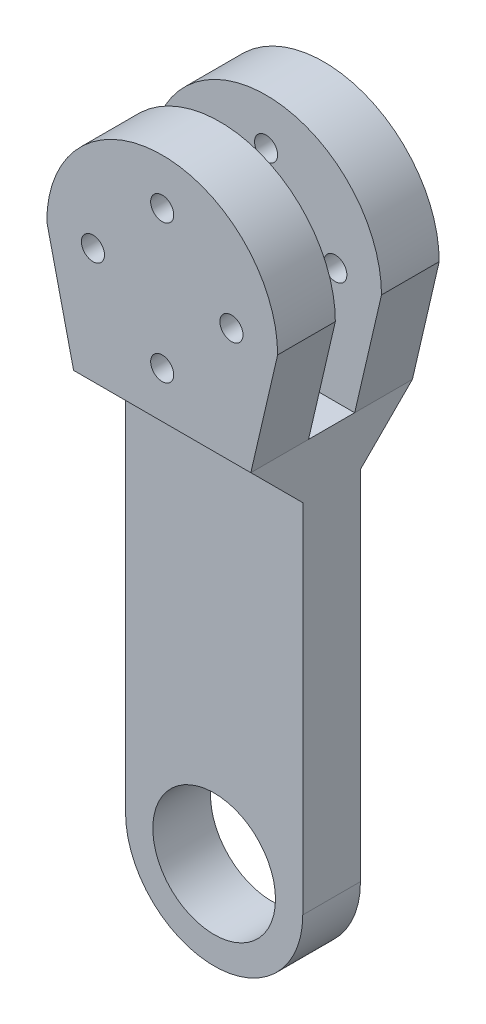
SolidWorks part; units mm, degrees
ref_plane "Front Plane" through (0, 0, 0) normal (0, 0, 1) x (1, 0, 0)
ref_plane "Top Plane" through (0, 0, 0) normal (0, 1, 0) x (1, 0, 0)
ref_plane "Right Plane" through (0, 0, 0) normal (1, 0, 0) x (0, 0, -1)
sketch "Sketch1" plane through (0, 0, 0) normal (0, 0, 1) x (1, 0, 0)
  line L0 (-9.75, 0) -> (-9.75, 45)
  line L1 (-9.75, 45) -> (9.75, 45)
  line L2 (9.75, 45) -> (9.75, 0)
  circle A0 centre (0, 0) radius 6.75
  arc A1 (-9.75, 0) -> (9.75, 0) centre (0, 0) ccw
  circle A2 centre (0, 0) radius 9.75 construction
  dimension "D1" = 13.5
  dimension "D3" = 45
  dimension "D2" = 3
extrude "Boss-Extrude1" add sketch "Sketch1" along normal mid plane 6.35
sketch "Sketch4" plane through (0, 0, 0) normal (0, 0, 1) x (1, 0, 0)
  line L0 (9.75, 45) -> (-9.75, 45) construction
  line L1 (-12.7, 57.7) -> (-9.75, 45)
  line L2 (12.7, 57.7) -> (9.75, 45)
  line L3 (-9.75, 45) -> (9.75, 45)
  arc A0 (12.7, 57.7) -> (-12.7, 57.7) centre (0, 57.7) ccw
  circle A1 centre (0, 65.32) radius 1.27
  circle A2 centre (7.62, 57.7) radius 1.27
  circle A3 centre (0, 50.08) radius 1.27
  circle A4 centre (-7.62, 57.7) radius 1.27
  dimension "D1" = 25.4
  dimension "D2" = 2.54
  dimension "D3" = 7.62
  dimension "D4" = 4
extrude "Boss-Extrude2" add sketch "Sketch4" along normal mid plane 17.78
chamfer "Chamfer1" distance 5.71 angle 45 2 edges at (0, 45, 3.175) (0, 45, -3.175)
sketch "Sketch5" plane through (0, 0, 0) normal (0, 0, 1) x (1, 0, 0)
  line L0 (-12.7, 57.7) -> (-9.75, 45)
  line L1 (-9.75, 45) -> (9.75, 45)
  line L2 (9.75, 45) -> (12.7, 57.7)
  arc A0 (12.7, 57.7) -> (-12.7, 57.7) centre (0, 57.7) ccw
extrude "Cut-Extrude1" cut sketch "Sketch5" against normal mid plane 5.08
